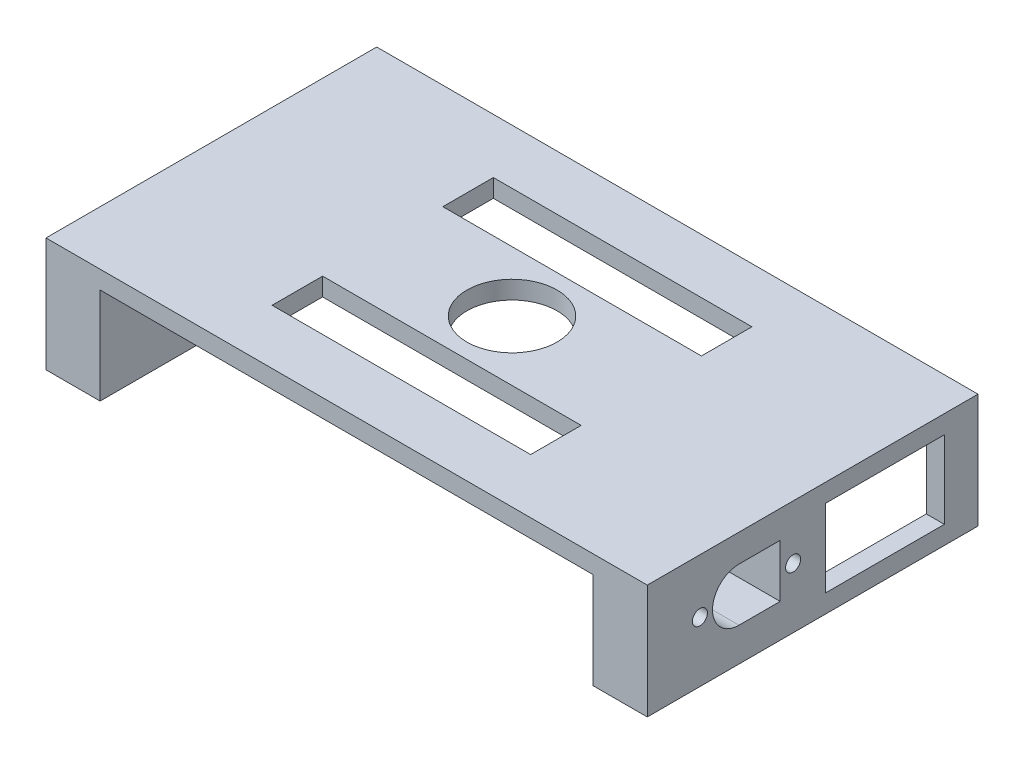
SolidWorks part; units mm, degrees
ref_plane "Front Plane" through (0, 0, 0) normal (0, 0, 1) x (1, 0, 0)
ref_plane "Top Plane" through (0, 0, 0) normal (0, 1, 0) x (1, 0, 0)
ref_plane "Right Plane" through (0, 0, 0) normal (1, 0, 0) x (0, 0, -1)
sketch "Sketch1" plane through (0, 0, 0) normal (0, 1, 0) x (1, 0, 0)
  line L1 (-50, -27.5) -> (50, -27.5)
  line L2 (-50, -27.5) -> (-50, 27.5)
  line L3 (-50, 27.5) -> (50, 27.5)
  line L4 (50, -27.5) -> (50, 27.5)
  line L5 (-50, -27.5) -> (50, 27.5) construction
  line L6 (-50, 27.5) -> (50, -27.5) construction
  point P0 (0, 0)
  dimension "D1" = 100
  dimension "D2" = 55
extrude "Boss-Extrude1" add sketch "Sketch1" along normal blind 19
sketch "Sketch2" plane through (0, 0, 0) normal (0, -1, 0) x (1, 0, 0)
  line L1 (-41, -45.5) -> (41, -45.5)
  line L2 (-41, -45.5) -> (-41, 45.5)
  line L3 (-41, 45.5) -> (41, 45.5)
  line L4 (41, -45.5) -> (41, 45.5)
  line L5 (-41, -45.5) -> (41, 45.5) construction
  line L6 (-41, 45.5) -> (41, -45.5) construction
  point P0 (0, 0)
  dimension "D1" = 91
  dimension "D2" = 82
extrude "Cut-Extrude1" cut sketch "Sketch2" against normal blind 16
sketch "Sketch3" plane through (50, 0, 0) normal (1, 0, 0) x (0, 0, -1)
  line L3 (-5.4, 5.6) -> (-5.4, 14.4)
  line L4 (-5.4, 5.6) -> (-12.25, 5.6)
  line L9 (-5.4, 14.4) -> (-12.25, 14.4)
  arc A1 (-12.25, 5.6) -> (-12.25, 14.4) centre (-12.25, 10) cw
  circle A2 centre (-18.75, 10) radius 1.25
  circle A3 centre (-3.25, 10) radius 1.25
  point P17 (-11, 10)
extrude "Cut-Extrude3" cut sketch "Sketch3" against normal up to next
sketch "Sketch15" plane through (50, 0, 0) normal (1, 0, 0) x (0, 0, -1)
  line L0 (0, 0) -> (0, 19) construction
  line L1 (-27.5, 19) -> (27.5, 19) construction
  line L2 (0, 9.5) -> (12, 9.5) construction
  line L4 (2.1, 3.05) -> (21.9, 3.05)
  line L5 (2.1, 3.05) -> (2.1, 15.95)
  line L6 (2.1, 15.95) -> (21.9, 15.95)
  line L7 (21.9, 3.05) -> (21.9, 15.95)
  line L8 (2.1, 3.05) -> (21.9, 15.95) construction
  line L9 (2.1, 15.95) -> (21.9, 3.05) construction
  dimension "D1" = 12
  dimension "D2" = 19.8
  dimension "D3" = 12.9
extrude "Cut-Extrude13" cut sketch "Sketch15" against normal up to next
sketch "Sketch6" plane through (0, 19, 0) normal (0, 1, 0) x (1, 0, 0)
  line L0 (0, 0) -> (0, -10) construction
  line L1 (21.5, -10) -> (-21.5, -10)
  line L2 (-21.5, -10) -> (-21.5, -18.4)
  line L3 (21.5, -10) -> (21.5, -18.4)
  line L4 (21.5, -18.4) -> (-21.5, -18.4)
  line L5 (0, 0) -> (5, 0) construction
  line L6 (21.5, 10) -> (21.5, 18.4)
  line L7 (21.5, 10) -> (-21.5, 10)
  line L8 (-21.5, 10) -> (-21.5, 18.4)
  line L9 (21.5, 18.4) -> (-21.5, 18.4)
  circle A0 centre (0, 0) radius 7.5
  point P6 (0, -10)
  dimension "D5" = 15
  dimension "D1" = 10
  dimension "D2" = 43
  dimension "D3" = 8.4
  dimension "D4" = 5
extrude "Cut-Extrude14" cut sketch "Sketch6" against normal up to next
sketch "Sketch16" plane through (0, 0, 0) normal (0, -1, 0) x (1, 0, 0)
  line L1 (41, -27.5) -> (47, -27.5)
  line L2 (41, -27.5) -> (41, 0)
  line L3 (41, 0) -> (47, 0)
  line L4 (47, -27.5) -> (47, 0)
  dimension "D1" = 6
  dimension "D2" = 27.5
extrude "Cut-Extrude15" cut sketch "Sketch16" against normal blind 16
sketch "Sketch17" [suppressed] plane through (0, 0, 0) normal (0, -1, 0) x (1, 0, 0)
  line L1 (41, 27.5) -> (-50, 27.5)
  line L2 (41, 27.5) -> (41, -27.5)
  line L3 (41, -27.5) -> (-50, -27.5)
  line L4 (-50, 27.5) -> (-50, -27.5)
extrude "Cut-Extrude16" [suppressed] cut sketch "Sketch17" against normal through all
